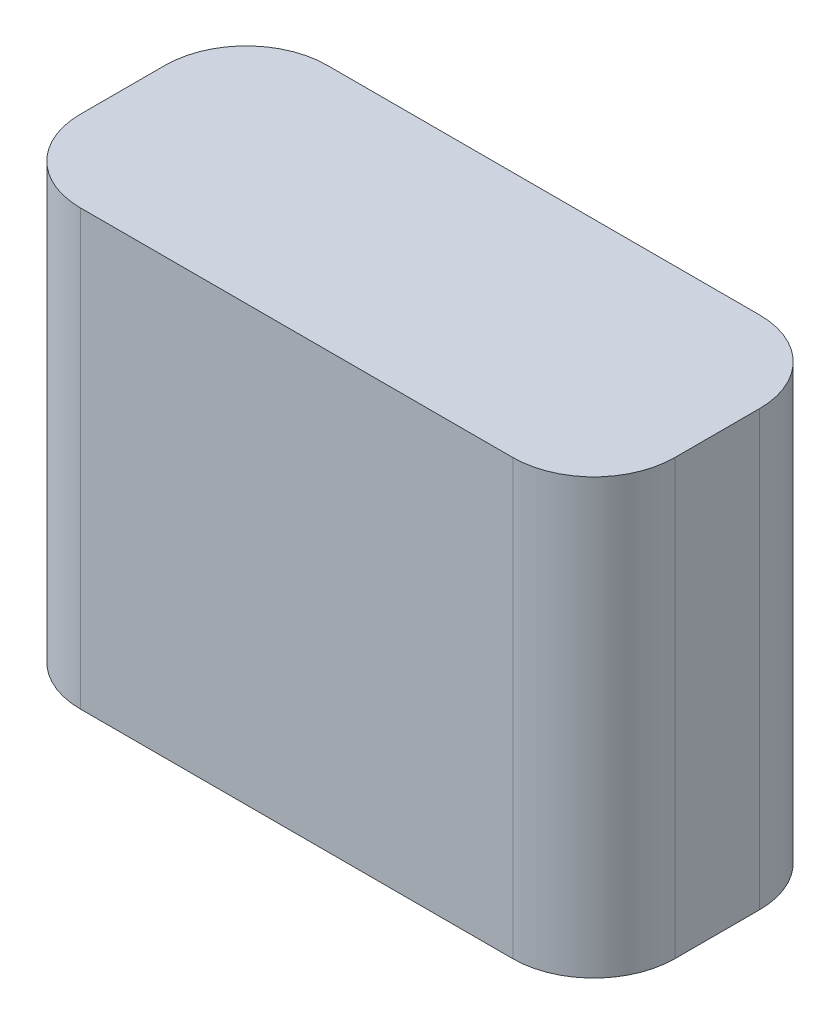
SolidWorks part; units mm, degrees
material "Gray Cast Iron"
ref_plane "Front" through (0, 0, 0) normal (0, 0, 1) x (1, 0, 0)
ref_plane "Top" through (0, 0, 0) normal (0, 1, 0) x (1, 0, 0)
ref_plane "Right" through (0, 0, 0) normal (1, 0, 0) x (0, 0, -1)
sketch "Sketch1" plane through (0, 0, 0) normal (0, 1, 0) x (1, 0, 0)
  line L1 (-36.703, -15.24) -> (36.703, -15.24)
  line L2 (-36.703, -15.24) -> (-36.703, 15.24)
  line L3 (-36.703, 15.24) -> (36.703, 15.24)
  line L4 (36.703, -15.24) -> (36.703, 15.24)
  line L5 (-36.703, -15.24) -> (36.703, 15.24) construction
  line L6 (-36.703, 15.24) -> (36.703, -15.24) construction
  point P0 (0, 0)
  dimension "D1" = 30.48
  dimension "D2" = 73.406
extrude "Boss-Extrude1" add sketch "Sketch1" along normal blind 53.594
fillet "Fillet1" radius 10 4 edges at (36.703, 26.797, 15.24) (36.703, 26.797, -15.24) (-36.703, 26.797, -15.24) (-36.703, 26.797, 15.24)
